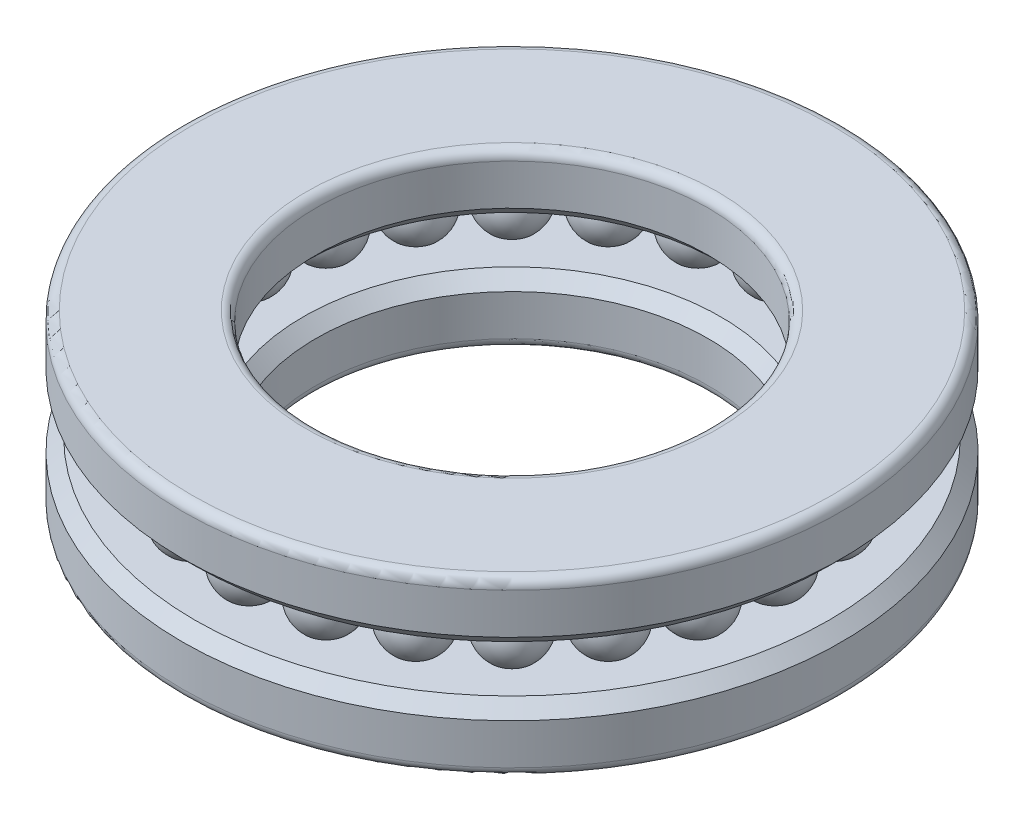
SolidWorks part; units mm, degrees
ref_plane "Front Plane" through (0, 0, 0) normal (0, 0, 1) x (1, 0, 0)
ref_plane "Top Plane" through (0, 0, 0) normal (0, 1, 0) x (1, 0, 0)
ref_plane "Right Plane" through (0, 0, 0) normal (1, 0, 0) x (0, 0, -1)
sketch "Sketch1" plane through (0, 0, 0) normal (1, 0, 0) x (0, 0, -1)
  line L0 (0, 0) -> (0, 11.4419) construction
  line L1 (0, 0) -> (-16.75, 0) construction
  line L2 (-16.75, 0) -> (-16.75, 9.5826) construction
  line L3 (-16.75, 2) -> (-16.75, -2)
  line L4 (-12.5, 0) -> (-12.5, -11.7804) construction
  line L5 (-21, 0) -> (-21, -11.35) construction
  line L6 (-21, -5.675) -> (-12.5, -5.675) construction
  arc A0 (-16.75, 2) -> (-16.75, -2) centre (-16.75, 0) ccw
  point P13 (-16.75, -5.675)
  dimension "D1" = 33.5
  dimension "D2" = 4
  dimension "D3" = 12.5
  dimension "D4" = 21
revolve "Revolve4" add sketch "Sketch1" angle 360 about L2
sketch "Sketch3" plane through (0, 0, 0) normal (1, 0, 0) x (0, 0, -1)
  line L0 (0, 0) -> (0, 7.9818) construction
  line L1 (-21, 5.5) -> (-21, 1.5)
  line L2 (-21, 1.5) -> (-12.5, 1.5)
  line L3 (-12.5, 1.5) -> (-12.5, 5.5)
  line L4 (0, 0) -> (0, -6.0195) construction
  line L5 (-12.5, 5.5) -> (-21, 5.5)
  line L6 (-21, -1.5) -> (-12.5, -1.5)
  line L7 (-12.5, -1.5) -> (-12.5, -5.5)
  line L8 (-12.5, -5.5) -> (-21, -5.5)
  line L9 (-21, -5.5) -> (-21, -1.5)
  line L10 (-12.5, 1.5) -> (-12.5, -1.5) construction
  line L11 (-12.5, 0) -> (0, 0) construction
  dimension "D1" = 11
  dimension "D2" = 25
  dimension "D3" = 42
  dimension "D4" = 4
revolve "Revolve5" add sketch "Sketch3" angle 360 about L0
pattern_circular "CirPattern2" count 24 over 360 about axis through (0, 5.5, 0) along (0, -1, 0) of "Revolve4"
fillet "Fillet1" radius 0.6 4 edges at (0, -5.5, -12.5) (0, -5.5, -21) (0, 5.5, -12.5) (0, 5.5, -21)
chamfer "Chamfer1" distance 0.8 angle 45 4 edges at (0, -1.5, -12.5) (0, 1.5, -12.5) (0, 1.5, -21) (0, -1.5, -21)
